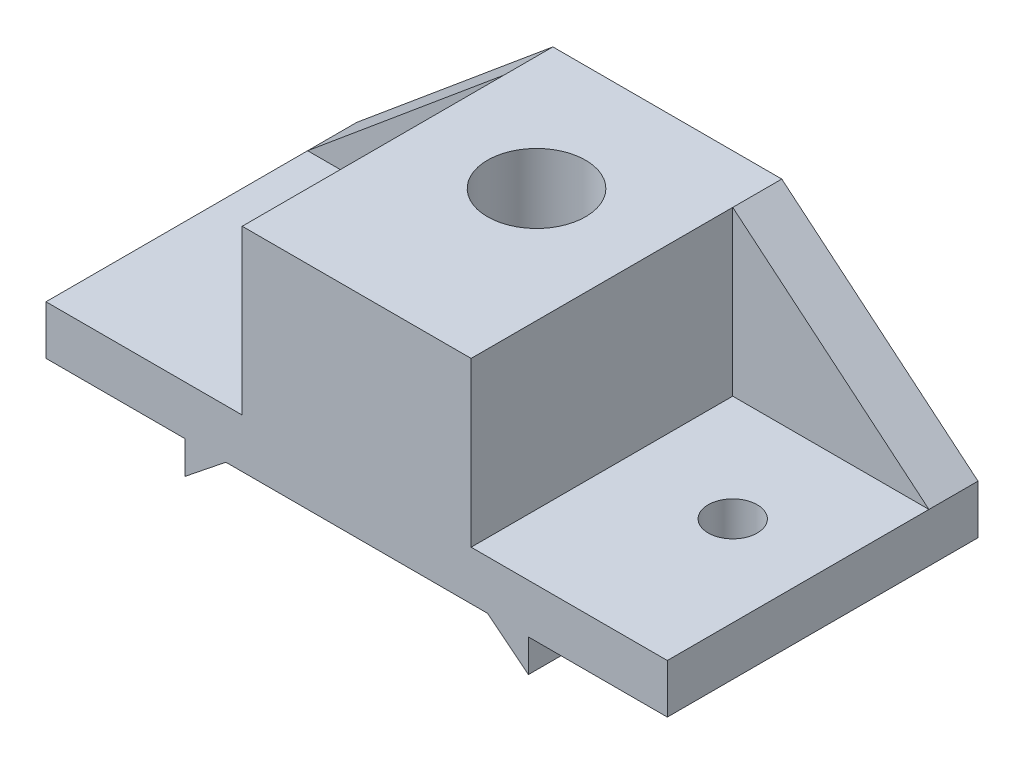
SolidWorks part; units mm, degrees
ref_plane "Front Plane" through (0, 0, 0) normal (0, 0, 1) x (1, 0, 0)
ref_plane "Top Plane" through (0, 0, 0) normal (0, 1, 0) x (1, 0, 0)
ref_plane "Right Plane" through (0, 0, 0) normal (1, 0, 0) x (0, 0, -1)
sketch "Sketch1" plane through (0, 0, 0) normal (0, 0, 1) x (1, 0, 0)
  line L0 (24, 26) -> (0, 6)
  line L9 (0, 0) -> (76, 0)
  line L10 (0, 0) -> (0, 6)
  line L15 (0, 6) -> (24, 6)
  line L16 (76, 0) -> (76, 6)
  line L18 (24, 6) -> (24, 26)
  line L19 (24, 26) -> (52, 26)
  line L20 (52, 6) -> (52, 26)
  line L21 (52, 26) -> (76, 6)
  line L22 (38, 6) -> (38, -18.2274) construction
  line L23 (59, 0) -> (59, -4)
  line L24 (59, -4) -> (54, 0)
  line L25 (17, 0) -> (17, -4)
  line L26 (17, -4) -> (22, 0)
  line L27 (52, 6) -> (76, 6)
  dimension "D1" = 28
  dimension "D2" = 76
  dimension "D3" = 5
  dimension "D4" = 4
  dimension "D5" = 17
  dimension "D6" = 30
  dimension "D7" = 6
  dimension "D8" = 4
  dimension "D9" = 5
  dimension "D10" = 17
extrude "Boss-Extrude2" add sketch "Sketch1" along normal blind 38 contours L25 L26 L9 | L24 L23 L9 | L27 L20 L19 L18 L15 L10 L9 L16 region at (38, 10.1654, 0) region at (18.6667, -1.3333, 0) region at (57.3333, -1.3333, 0)
extrude "Boss-Extrude3" add sketch "Sketch1<4>" along normal blind 6 contours L20 L27 L21 | L15 L18 L0 region at (16, 12.6667, 0) region at (60, 12.6667, 0)
sketch "Sketch1<4>" plane through (0, 0, 0) normal (0, 0, 1) x (1, 0, 0) same geometry as "Sketch1"
sketch "Sketch6" plane through (0, 26, 0) normal (0, 1, 0) x (1, 0, 0)
  line L0 (38, 0) -> (38, -40.3016) construction
  line L1 (24, 0) -> (52, 0) construction
  line L2 (52, -38) -> (76, -38) construction
  line L3 (76, -38) -> (76, -6) construction
  circle A0 centre (38, -16) radius 6
  circle A1 centre (65, -19) radius 3
  circle A3 centre (11, -19) radius 3
  dimension "D2" = 12
  dimension "D4" = 6
  dimension "D5" = 11
  dimension "D1" = 16
  dimension "D3" = 19
extrude "Cut-Extrude1" cut sketch "Sketch6" against normal through all
